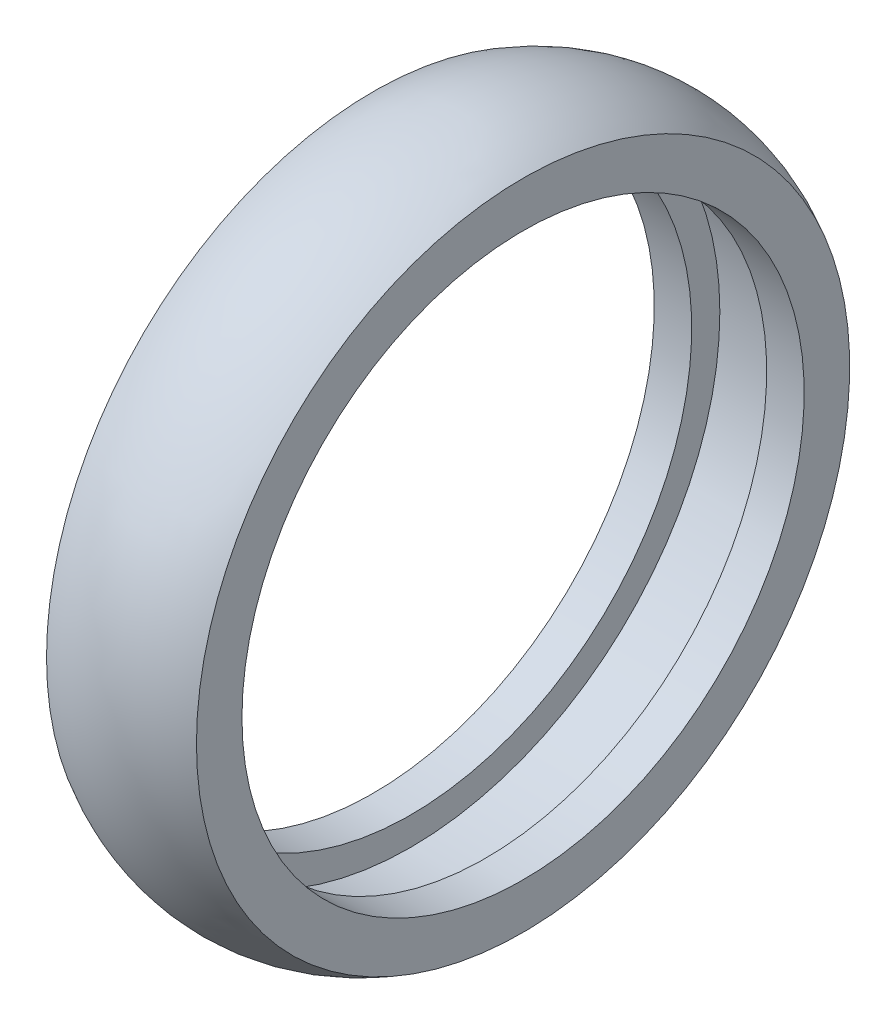
SolidWorks part; units mm, degrees
ref_plane "Front Plane" through (0, 0, 0) normal (0, 0, 1) x (1, 0, 0)
ref_plane "Top Plane" through (0, 0, 0) normal (0, 1, 0) x (1, 0, 0)
ref_plane "Right Plane" through (0, 0, 0) normal (1, 0, 0) x (0, 0, -1)
sketch "Sketch1" plane through (0, 0, 0) normal (0, 0, 1) x (1, 0, 0)
  line L0 (-690.4668, 0) -> (33832.8751, 0) construction
  line L1 (0, -690.4668) -> (0, 33832.8751) construction
  line L2 (4, 33) -> (-4, 33)
  line L3 (-4, 33) -> (-4, 30)
  line L4 (-4, 30) -> (-8, 30)
  line L5 (-8, 30) -> (-8, 34.8564)
  line L7 (8, 30) -> (8, 34.8564)
  line L8 (4, 30) -> (8, 30)
  line L9 (4, 33) -> (4, 30)
  arc A0 (-8, 34.8564) -> (8, 34.8564) centre (0, 21) cw
  dimension "D6" = 16
  dimension "D1" = 66
  dimension "D3" = 4
  dimension "D4" = 8
  dimension "D5" = 3
  dimension "D2" = 4
revolve "Revolve1" add sketch "Sketch1" angle 360 about L0
equation "\"width\"= 24"
equation "\"thk\"= 3"
equation "\"holesize\"= 4.2"
equation "\"holedistance\"= ( 20 + 12 ) / 2"
equation "\"threaded_hole\"= 3.9"
equation "\"fillet_radius\"= 2"
equation "\"ground_clearance\"= 25"
equation "\"tire_thk\"= 4"
equation "\"innerwheel_diam\" = \"wheel_diam\"-2*\"tire_thk\""
equation "\"innerwheel_thk\"= 8"
equation "\"wheel_diam\"= 2*(\"width\"/2+\"ground_clearance\")"
equation "\"D1@Sketch1\"=\"innerwheel_diam\""
equation "\"D3@Sketch1\"=\"D2@Sketch1\""
equation "\"D4@Sketch1\"=\"innerwheel_thk\""
equation "\"D2@Sketch1\"=\"tire_thk\""
